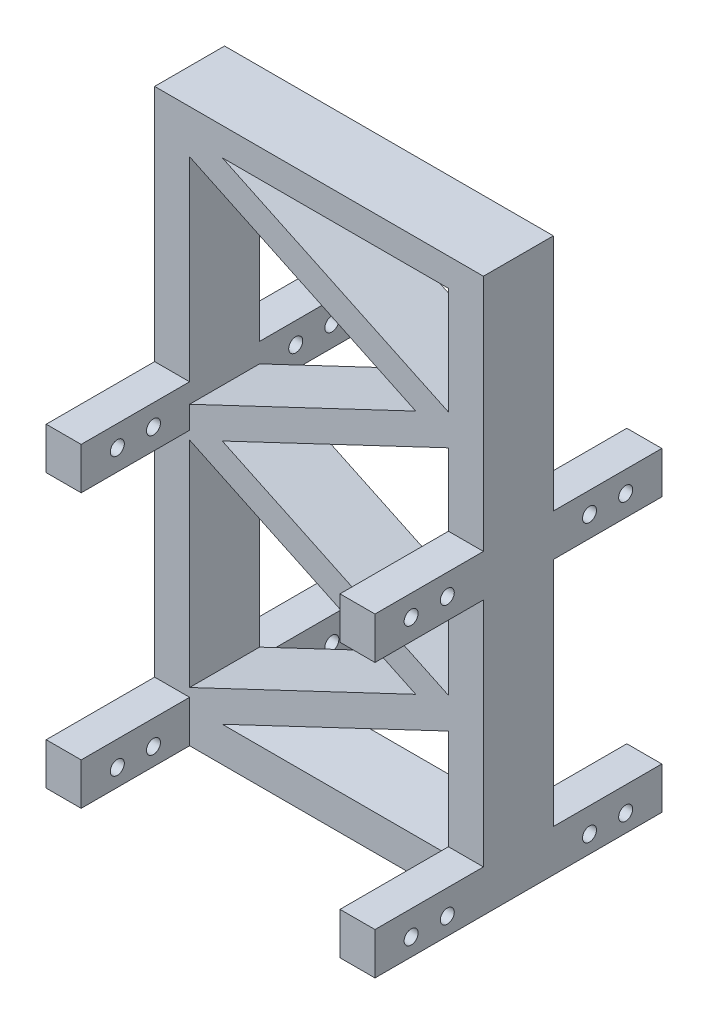
SolidWorks part; units mm, degrees
note: The reader was unsure of these and kept them because the rebuilt part matched: shared geometry of "스케치2<2>".
ref_plane "정면" through (0, 0, 0) normal (0, 0, 1) x (1, 0, 0)
ref_plane "윗면" through (0, 0, 0) normal (0, 1, 0) x (1, 0, 0)
ref_plane "우측면" through (0, 0, 0) normal (1, 0, 0) x (0, 0, -1)
sketch "스케치1" plane through (0, 0, 0) normal (0, 0, 1) x (1, 0, 0)
  line L0 (-15, 0.1156) -> (22, 0.1156) construction
  line L1 (-15, 35.1806) -> (22, 35.1806)
  line L2 (-15, 35.1806) -> (-15, -34.9494)
  line L3 (-15, -34.9494) -> (22, -34.9494)
  line L4 (22, 35.1806) -> (22, -34.9494)
  line L5 (-15, 17.6481) -> (22, 17.6481) construction
  line L6 (-15, -17.4169) -> (22, -17.4169) construction
  line L7 (-20, 39.1806) -> (27, 39.1806)
  line L8 (-20, 39.1806) -> (-20, -39.9494)
  line L9 (-20, -39.9494) -> (27, -39.9494)
  line L10 (27, 39.1806) -> (27, -39.9494)
  line L11 (-15, 35.1806) -> (22, 17.6481) construction
  line L12 (22, 17.6481) -> (-15, 0.1156) construction
  line L13 (22, -17.4169) -> (-15, 0.1156) construction
  line L14 (-15, -34.9494) -> (22, -17.4169) construction
  line L15 (-15, 32.9674) -> (22, 15.4349)
  line L16 (-10.3294, 35.1806) -> (22, 19.8613)
  line L17 (22, 19.8613) -> (-15, 2.3288)
  line L18 (22, 15.4349) -> (-15, -2.0976)
  line L19 (-15, 2.3288) -> (22, -15.2037)
  line L20 (-15, -2.0976) -> (22, -19.6301)
  line L21 (22, -15.2037) -> (-15, -32.7362)
  line L22 (22, -19.6301) -> (-10.3294, -34.9494)
  point P0 (0, 0)
  dimension "D1" = 70.13
  dimension "D2" = 5
  dimension "D3" = 4
  dimension "D4" = 5
  dimension "D5" = 5
  dimension "D6" = 47
  dimension "D7" = 17.5325
  dimension "D8" = 17.5325
  dimension "D9" = 2
  dimension "D10" = 2
  dimension "D11" = 2
  dimension "D12" = 2
  dimension "D13" = 2
  dimension "D14" = 2
  dimension "D15" = 2
  dimension "D16" = 2
extrude "보스-돌출2" add sketch "스케치1" along normal blind 10 contours L10 L7 L8 L9 L1 L4 L3 L2 | L17 L16 L1 L2 L15 | L4 L17 L15 | L17 L19 L18 L15 | L19 L2 L18 | L21 L19 L18 L20 | L4 L21 L20 | L22 L20 L21 L2 L3
sketch "스케치2" plane through (27, 0, 0) normal (1, 0, 0) x (0, 0, -1)
  line L0 (-10, -39.9494) -> (-25.5, -39.9494)
  line L1 (-25.5, -39.9494) -> (-25.5, -33.9494)
  line L2 (-25.5, -33.9494) -> (-10, -33.9494)
  line L3 (-10, -33.9494) -> (-10, -39.9494)
  line L4 (0, -39.9494) -> (15.5, -39.9494)
  line L5 (15.5, -39.9494) -> (15.5, -33.9494)
  line L6 (15.5, -33.9494) -> (0, -33.9494)
  line L12 (0, -33.9494) -> (0, -39.9494)
  line L13 (-10, 39.1806) -> (-10, -39.9494) construction
  line L15 (-10, -0.8894) -> (-25.5, -0.8894)
  line L16 (-10, -0.8894) -> (-10, 5.1106)
  line L17 (-10, -39.9494) -> (0, -39.9494) construction
  line L18 (-10, 5.1106) -> (-25.5, 5.1106)
  line L19 (-25.5, -0.8894) -> (-25.5, 5.1106)
  line L20 (0, 39.1806) -> (0, -39.9494) construction
  line L21 (0, -0.8894) -> (15.5, -0.8894)
  line L22 (0, -0.8894) -> (0, 5.1106)
  line L23 (0, 5.1106) -> (15.5, 5.1106)
  line L24 (15.5, -0.8894) -> (15.5, 5.1106)
  circle A0 centre (-20.3333, 2.1106) radius 1
  circle A1 centre (-15.1667, 2.1106) radius 1
  circle A2 centre (5.1667, 2.1106) radius 1
  circle A3 centre (10.3333, 2.1106) radius 1
  circle A4 centre (-20.3333, -37.4494) radius 1
  circle A5 centre (-15.1667, -37.4494) radius 1
  circle A6 centre (5.1667, -37.4494) radius 1
  circle A7 centre (10.3333, -37.4494) radius 1
  point P42 (-10, -34.9494)
  point P43 (0, 0)
  dimension "D10" = 2
  dimension "D11" = 2
  dimension "D16" = 2
  dimension "D17" = 2
  dimension "D22" = 2
  dimension "D23" = 2
  dimension "D28" = 2
  dimension "D29" = 2
  dimension "D1" = 15.5
  dimension "D2" = 15.5
  dimension "D3" = 6
  dimension "D4" = 15.5
  dimension "D5" = 15.5
  dimension "D6" = 6
  dimension "D7" = 6
  dimension "D8" = 39.06
  dimension "D9" = 39.06
  dimension "D12" = 3
  dimension "D13" = 3
  dimension "D14" = 5.1667
  dimension "D15" = 5.1667
  dimension "D18" = 3
  dimension "D19" = 3
  dimension "D20" = 5.1667
  dimension "D21" = 5.1667
  dimension "D24" = 2.5
  dimension "D25" = 2.5
  dimension "D26" = 5.1667
  dimension "D27" = 5.1667
  dimension "D30" = 5.1667
  dimension "D31" = 5.1667
  dimension "D32" = 2.5
  dimension "D33" = 2.5
  dimension "D34" = 0
  dimension "D35" = 6
extrude "보스-돌출3" add sketch "스케치2" against normal up to surface (5 mm away) up to face at (22, 0.1156, 5)
extrude "보스-돌출4" add sketch "스케치2<2>" against normal up to surface (5 mm away) from surface at -42 contours L23 L24 L21 L22
sketch "스케치2<2>" plane through (27, 0, 0) normal (1, 0, 0) x (0, 0, -1) same geometry as "스케치2"
